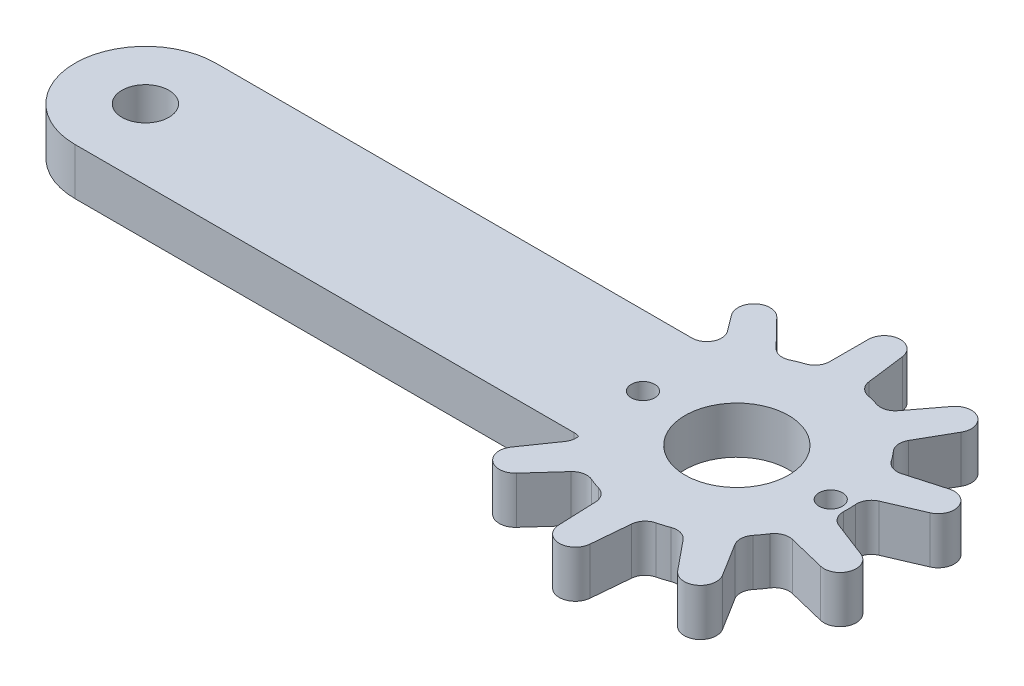
SolidWorks part; units mm, degrees
ref_plane "Alzado" through (0, 0, 0) normal (0, 0, 1) x (1, 0, 0)
ref_plane "Planta" through (0, 0, 0) normal (0, 1, 0) x (1, 0, 0)
ref_plane "Vista lateral" through (0, 0, 0) normal (1, 0, 0) x (0, 0, -1)
sketch "Croquis1" plane through (0, 0, 0) normal (0, 1, 0) x (1, 0, 0)
  line L1 (-20, 0) -> (20, 0)
  line L3 (-20, -9.525) -> (20, -9.525)
  arc A0 (-20, 0) -> (-20, -9.525) centre (-20, -4.7625) ccw
  arc A1 (20, -9.525) -> (20, 0) centre (20, -4.7625) ccw
  circle A2 centre (-20, -4.7625) radius 1.5875
  circle A3 centre (20, -4.7625) radius 1.5875
  dimension "D3" = 4.7625
  dimension "D5" = 3.175
  dimension "D6" = 3.175
  dimension "D1" = 40
  dimension "D2" = 9.525
  dimension "D4" = 40
extrude "Saliente-Extruir1" add sketch "Croquis1" along normal blind 3.175
sketch "Croquis2" plane through (0, 3.175, 0) normal (0, 1, 0) x (1, 0, 0)
  line L0 (20, -1004.7625) -> (20, 48995.2375) construction
  circle A0 centre (20, -4.7625) radius 7.5
  circle A1 centre (20, 14.7375) radius 9 construction
  circle A2 centre (20, -4.7625) radius 1.5875
  dimension "D1" = 15
  dimension "D2" = 18
  dimension "D3" = 19.5
extrude "Saliente-Extruir2" add sketch "Croquis2" against normal blind 3.175
sketch "Croquis7" plane through (0, 3.175, 0) normal (0, 1, 0) x (1, 0, 0)
  circle A0 centre (20, -4.7625) radius 3.5
  circle A1 centre (13.65, -4.7625) radius 0.7937
  circle A2 centre (26.35, -4.7625) radius 0.7937
  dimension "D1" = 7
  dimension "D2" = 1.5875
  dimension "D3" = 1.5875
  dimension "D4" = 6.35
  dimension "D5" = 6.35
extrude "Cortar-Extruir3" cut sketch "Croquis7" against normal blind 10
sketch "Croquis8" plane through (0, 3.175, 0) normal (0, 1, 0) x (1, 0, 0)
  line L0 (20, -4.7625) -> (-29071.9665, 40660.4252) construction
  line L1 (20, -4.7625) -> (-22676.5039, 22236.8096) construction
  line L2 (20, -4.7625) -> (-23649.2675, 19451.2229) construction
  line L3 (20, -4.7625) -> (-25417.0581, 43041.2138) construction
  line L4 (11.6078, 3.4615) -> (14.2062, 0)
  line L6 (13.1634, 4.7938) -> (16.1844, 1.6944)
  arc A1 (16.1844, 1.6944) -> (14.2062, 0) centre (20, -4.7625) ccw
  arc A2 (13.1634, 4.7938) -> (11.6078, 3.4615) centre (20, -4.7625) ccw
  arc A3 (14.2062, -9.525) -> (14.2062, 0) centre (20, -4.7625) ccw construction
  dimension "D1" = 23.5
  dimension "D2" = 5
  dimension "D3" = 10
  dimension "D4" = 5
extrude "Saliente-Extruir3" add sketch "Croquis8" against normal blind 3.175
sketch "Croquis9" plane through (0, 3.175, 0) normal (0, 1, 0) x (1, 0, 0)
  line L0 (16.1844, 1.6944) -> (13.1634, 4.7938) construction
  line L1 (11.6078, 3.4615) -> (14.2062, 0) construction
  line L2 (11.6078, 3.4615) -> (12.194, 2.6806)
  line L3 (13.8449, 4.0946) -> (13.1634, 4.7938)
  arc A0 (13.8449, 4.0946) -> (12.194, 2.6806) centre (13.065, 3.3344) ccw
  arc A1 (13.1634, 4.7938) -> (11.6078, 3.4615) centre (20, -4.7625) ccw construction
  arc A2 (13.1634, 4.7938) -> (11.6078, 3.4615) centre (20, -4.7625) ccw
  line M6 (16.1844, 1.6944) -> (13.1634, 4.7938)
  arc M7 (13.1634, 4.7938) -> (11.6078, 3.4615) centre (20, -4.7625) ccw
  line M8 (11.6078, 3.4615) -> (14.2062, 0)
extrude "Cortar-Extruir4" cut sketch "Croquis9" against normal blind 10 contours A0 M7 M8 | A0 M6 M7 region at (11.8961, 3.175, -3.4495) region at (13.1309, 3.175, -4.5071)
pattern_circular "MatrizC1" count 8 every 37 about axis through (20, 0, 4.7625) along (0, 1, 0) of "Saliente-Extruir3", "Cortar-Extruir4" reverse direction yes
fillet "Redondeo1" radius 1 17 edges at (14.2062, 1.5875, 9.525) (14.3898, 1.5875, 9.74) (16.4305, 1.5875, 11.3586) (18.515, 1.5875, 12.114) (21.1189, 1.5875, 12.1786) (23.2383, 1.5875, 11.5274) (25.3567, 1.5875, 10.0118) (26.6574, 1.5875, 8.2163) (27.4372, 1.5875, 5.7311) (27.3954, 1.5875, 3.5143) (26.5225, 1.5875, 1.0602) (20.8386, 1.5875, -2.6905) (22.981, 1.5875, -2.1196) (14.2062, 1.5875, 0) (18.239, 1.5875, -2.5278) (16.1844, 1.5875, -1.6944) (25.1551, 1.5875, -0.685)
